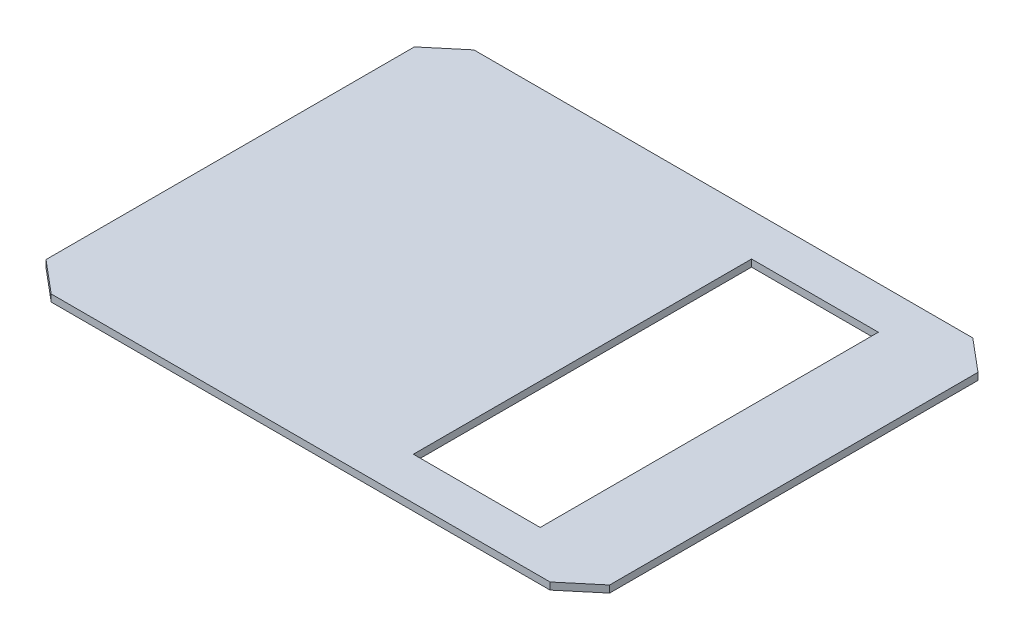
SolidWorks part; units mm, degrees
material "Thornel Mat VMA"
ref_plane "Front Plane" through (0, 0, 0) normal (0, 0, 1) x (1, 0, 0)
ref_plane "Top Plane" through (0, 0, 0) normal (0, 1, 0) x (1, 0, 0)
ref_plane "Right Plane" through (0, 0, 0) normal (1, 0, 0) x (0, 0, -1)
sketch "Sketch1" plane through (0, 0, 0) normal (0, 1, 0) x (1, 0, 0)
  line L0 (0, -95.25) -> (0, 95.25) construction
  line L1 (-127, 95.25) -> (127, 95.25) construction
  line L2 (-127, 95.25) -> (-127, -95.25) construction
  line L3 (-127, -95.25) -> (127, -95.25) construction
  line L4 (127, 95.25) -> (127, -95.25) construction
  line L5 (-127, 0) -> (127, 0) construction
  line L6 (-114.3, 0) -> (-114.3, 52.7344) construction
  line L7 (-114.3, 52.7344) -> (-101.6, 52.7344) construction
  line L8 (-101.6, 52.7344) -> (-87.0069, 64.9795) construction
  line L9 (-87.0069, 64.9795) -> (-87.0069, 76.2) construction
  line L10 (-87.0069, 76.2) -> (0, 76.2) construction
  line L11 (-127, 83.0049) -> (-112.4069, 95.25) construction
  line L12 (-87.0069, 64.9795) -> (-112.4069, 95.25) construction
  line L13 (-101.6, 52.7344) -> (-127, 83.0049) construction
  line L15 (-127, 95.25) -> (127, 95.25) construction
  line L16 (-127, 95.25) -> (-127, -95.25) construction
  line L17 (-127, -95.25) -> (127, -95.25) construction
  line L18 (127, 95.25) -> (127, -95.25) construction
  line L19 (-127, 95.25) -> (127, -95.25) construction
  line L20 (-127, -95.25) -> (127, 95.25) construction
  line L22 (127, -83.0049) -> (112.4069, -95.25)
  line L23 (-127, -83.0049) -> (-112.4069, -95.25)
  line L24 (-112.4069, 95.25) -> (112.4069, 95.25)
  line L25 (-127, -83.0049) -> (-127, 83.0049)
  line L26 (127, 83.0049) -> (127, -83.0049)
  line L27 (112.4069, -95.25) -> (-112.4069, -95.25)
  line L28 (-94.3034, 58.8569) -> (-119.7034, 89.1274) construction
  line L33 (-127, 83.0049) -> (-112.4069, 95.25)
  line L36 (127, 83.0049) -> (112.4069, 95.25)
  point P8 (0, 0)
  point P18 (0, 0)
  dimension "D1" = 190.5
  dimension "D2" = 254
  dimension "D3" = 12.7
  dimension "D4" = 19.05
  dimension "D5" = 12.7
  dimension "D6" = 40
  dimension "D7" = 19.05
  dimension "D8" = 0
  dimension "D9" = 12.7
extrude "Boss-Extrude1" add sketch "Sketch1" along normal blind 3.175 contours L27 L22 L26 L36 L24 L33 L25 L23 region at (0, 0, 0)
sketch "Sketch2" plane through (0, 3.175, 0) normal (0, 1, 0) x (1, 0, 0)
  line L0 (0, 0) -> (127, 0) construction
  line L1 (127, 83.0049) -> (127, -83.0049) construction
  line L3 (31.75, 76.2) -> (88.9, 76.2)
  line L4 (31.75, 76.2) -> (31.75, -76.2)
  line L5 (31.75, -76.2) -> (88.9, -76.2)
  line L6 (88.9, 76.2) -> (88.9, -76.2)
  line L7 (31.75, 76.2) -> (88.9, -76.2) construction
  line L8 (31.75, -76.2) -> (88.9, 76.2) construction
  point P5 (60.325, 0)
  dimension "D1" = 57.15
  dimension "D2" = 152.4
  dimension "D3" = 38.1
extrude "Cut-Extrude1" cut sketch "Sketch2" against normal through all
